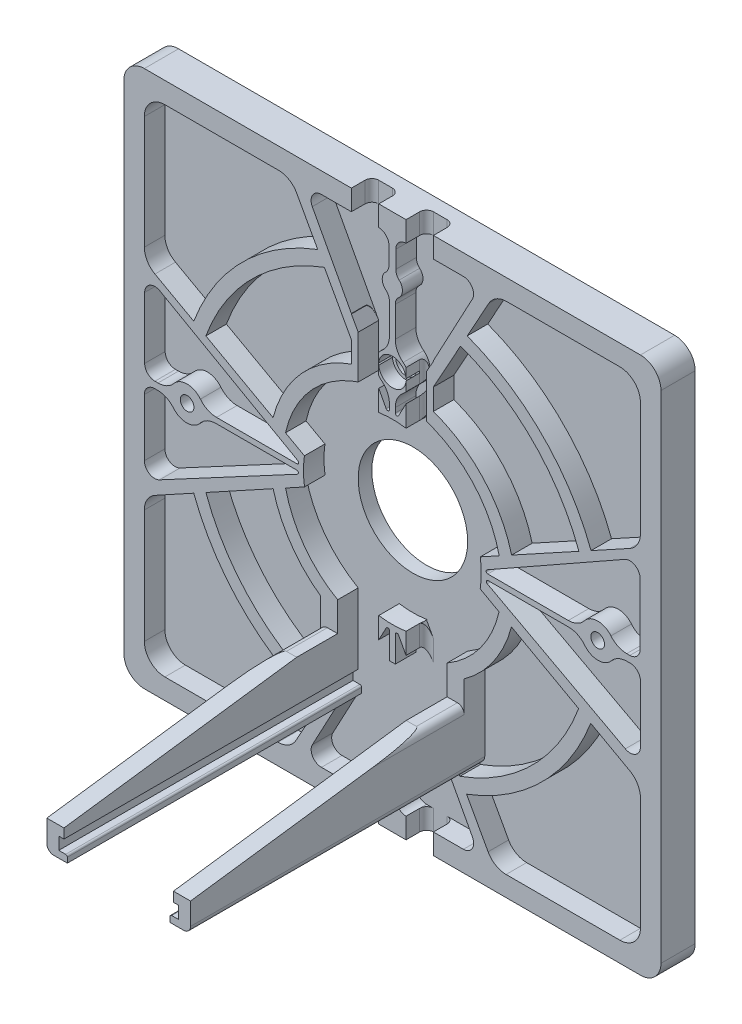
SolidWorks part; units mm, degrees
ref_plane "Спереди" through (0, 0, 0) normal (0, 0, 1) x (1, 0, 0)
ref_plane "Сверху" through (0, 0, 0) normal (0, 1, 0) x (1, 0, 0)
ref_plane "Справа" through (0, 0, 0) normal (1, 0, 0) x (0, 0, -1)
sketch "Эскиз1" plane through (0, 0, 0) normal (0, 0, 1) x (1, 0, 0)
  line L5 (-36.25, -39.25) -> (36.25, -39.25)
  line L6 (-39.25, -36.25) -> (-39.25, 36.25)
  line L7 (-36.25, 39.25) -> (36.25, 39.25)
  line L8 (39.25, -36.25) -> (39.25, 36.25)
  arc A0 (-36.25, -39.25) -> (-39.25, -36.25) centre (-36.25, -36.25) cw
  arc A1 (36.25, -39.25) -> (39.25, -36.25) centre (36.25, -36.25) ccw
  arc A2 (36.25, 39.25) -> (39.25, 36.25) centre (36.25, 36.25) cw
  arc A3 (-39.25, 36.25) -> (-36.25, 39.25) centre (-36.25, 36.25) cw
  dimension "D1" = 3
extrude "Бобышка-Вытянуть2" add sketch "Эскиз1" along normal blind 5
sketch "Эскиз6" plane through (0, 0, 5) normal (0, 0, 1) x (1, 0, 0)
  circle A0 centre (0, 0) radius 13
extrude "Вырез-Вытянуть2" cut sketch "Эскиз6" against normal blind 3
sketch "Эскиз10" plane through (0, 0, 5) normal (0, 0, 1) x (1, 0, 0)
  line L10 (-36.25, -33.25) -> (-36.25, -16.6195)
  line L11 (-33.25, -36.25) -> (-16.7128, -36.25)
  line L12 (-34.6933, -13.9895) -> (-12.8452, -2)
  line L13 (-14.0876, -34.7019) -> (-2, -12.8452)
  line L14 (-2, -12.8452) -> (-12.8452, -2)
  line L15 (36.2485, 33.2453) -> (36.2485, 16.6148)
  line L16 (33.2485, 36.2453) -> (16.7113, 36.2453)
  line L17 (34.6917, 13.9847) -> (12.8437, 1.9953)
  line L18 (14.086, 34.6972) -> (1.9985, 12.8405)
  line L19 (1.9985, 12.8405) -> (12.8437, 1.9953)
  line L20 (33.2453, -36.3173) -> (16.6148, -36.3173)
  line L21 (36.2453, -33.3173) -> (36.2453, -16.7802)
  line L22 (13.9847, -34.7606) -> (1.9953, -12.9126)
  line L23 (34.6972, -14.1549) -> (12.8405, -2.0673)
  line L24 (12.8405, -2.0673) -> (1.9953, -12.9126)
  line L25 (-33.25, 36.1811) -> (-16.6195, 36.1811)
  line L26 (-36.25, 33.1811) -> (-36.25, 16.644)
  line L27 (-13.9895, 34.6244) -> (-2, 12.7764)
  line L28 (-34.7019, 14.0187) -> (-12.8452, 1.9311)
  line L29 (-12.8452, 1.9311) -> (-2, 12.7764)
  circle A0 centre (0, 0) radius 13 construction
  arc A1 (-36.25, -16.6195) -> (-34.6933, -13.9895) centre (-33.25, -16.6195) cw
  arc A2 (-16.7128, -36.25) -> (-14.0876, -34.7019) centre (-16.7128, -33.25) ccw
  arc A3 (-36.25, -33.25) -> (-33.25, -36.25) centre (-33.25, -33.25) ccw
  arc A4 (36.2485, 16.6148) -> (34.6917, 13.9847) centre (33.2485, 16.6148) cw
  arc A5 (16.7113, 36.2453) -> (14.086, 34.6972) centre (16.7113, 33.2453) ccw
  arc A6 (36.2485, 33.2453) -> (33.2485, 36.2453) centre (33.2485, 33.2453) ccw
  arc A7 (16.6148, -36.3173) -> (13.9847, -34.7606) centre (16.6148, -33.3173) cw
  arc A8 (36.2453, -16.7802) -> (34.6972, -14.1549) centre (33.2453, -16.7802) ccw
  arc A9 (33.2453, -36.3173) -> (36.2453, -33.3173) centre (33.2453, -33.3173) ccw
  arc A10 (-16.6195, 36.1811) -> (-13.9895, 34.6244) centre (-16.6195, 33.1811) cw
  arc A11 (-36.25, 16.644) -> (-34.7019, 14.0187) centre (-33.25, 16.644) ccw
  arc A12 (-33.25, 36.1811) -> (-36.25, 33.1811) centre (-33.25, 33.1811) ccw
  point P34 (-36.25, -36.25)
  dimension "D1" = 3
extrude "Вырез-Вытянуть4" cut sketch "Эскиз10" against normal blind 3
sketch "Эскиз12" plane through (0, 0, 2) normal (0, 0, 1) x (1, 0, 0)
  circle A0 centre (0, 0) radius 18
  circle A1 centre (0, 0) radius 16
extrude "Бобышка-Вытянуть7" add sketch "Эскиз12" along normal blind 3
sketch "Эскиз18" plane through (0, 0, 2) normal (0, 0, 1) x (1, 0, 0)
  circle A0 centre (0, 0) radius 29
  circle A1 centre (0, 0) radius 31
extrude "Бобышка-Вытянуть10" add sketch "Эскиз18" along normal blind 3
sketch "Эскиз19" plane through (0, 0, 2) normal (0, 0, 1) x (1, 0, 0)
  circle A0 centre (-30, 0) radius 1
  circle A1 centre (30, 0) radius 1
extrude "Вырез-Вытянуть7" cut sketch "Эскиз19" against normal blind 2 and the other way blind 3
chamfer "Фаска6" distance 2 angle 45 2 edges at (-29, 0, 0) (31, 0, 0)
sketch "Эскиз21" plane through (0, 0, 5) normal (0, 0, 1) x (1, 0, 0)
  line L0 (-34.7046, 0.4543) -> (-34.2543, 0.4543)
  line L14 (-25.7046, 0.3762) -> (-13.9439, 0.3789)
  line L17 (-25.761, -0.4346) -> (-13.9898, -0.4346)
  line L18 (-33.9662, 12.24) -> (-13.8209, 0.8465)
  line L19 (-36.2046, 1.9543) -> (-36.2046, 10.9344)
  line L22 (-0.495, -34.7501) -> (-0.495, -32.2046)
  line L23 (-36.25, -2.0051) -> (-36.25, -10.3806)
  line L24 (-34.0421, -11.703) -> (-13.8718, -0.905)
  line L25 (-34.75, -0.5051) -> (-34.2952, -0.5051)
  line L26 (-0.4246, -27.7337) -> (-0.4246, -13.9898)
  line L27 (0.4345, -27.7337) -> (0.4345, -13.9898)
  line L28 (-11.693, -34.0421) -> (-0.895, -13.8718)
  line L29 (-1.995, -36.2501) -> (-10.3705, -36.2501)
  line L30 (2.005, -36.2501) -> (10.3805, -36.2501)
  line L31 (11.7029, -34.0421) -> (0.9049, -13.8718)
  line L32 (0.505, -34.7501) -> (0.505, -32.2046)
  line L38 (0.4928, 34.7538) -> (0.4928, 32.2084)
  line L44 (11.6908, 34.0458) -> (0.8928, 13.8756)
  line L45 (1.9928, 36.2538) -> (10.3683, 36.2538)
  line L46 (-2.0072, 36.2538) -> (-10.3827, 36.2538)
  line L47 (-11.7051, 34.0459) -> (-0.9071, 13.8756)
  line L48 (-0.5072, 34.7538) -> (-0.5072, 32.2084)
  line L50 (-0.4367, 13.9936) -> (-0.4367, 14.7298)
  line L51 (0.4224, 13.9936) -> (0.4224, 14.6764)
  line L52 (0.4224, 27.7375) -> (0.4224, 23.3236)
  line L53 (-0.4367, 27.7375) -> (-0.4367, 23.2702)
  line L54 (34.75, -0.5051) -> (34.2952, -0.5051)
  line L55 (36.25, -2.0051) -> (36.25, -10.3806)
  line L56 (34.0421, -11.703) -> (13.8718, -0.905)
  line L57 (25.761, -0.4346) -> (13.9898, -0.4346)
  line L58 (34.7046, 0.4543) -> (34.2543, 0.4543)
  line L59 (36.2046, 1.9543) -> (36.2046, 10.9344)
  line L60 (33.9662, 12.24) -> (13.8209, 0.8465)
  line L61 (25.7046, 0.3762) -> (13.9439, 0.3789)
  arc A8 (-12.855, 1.9365) -> (-12.8452, -2) centre (0, 0) ccw construction
  arc A9 (-12.855, 1.9365) -> (-12.8452, -2) centre (0, 0) ccw construction
  arc A15 (-36.25, -10.3806) -> (-34.0421, -11.703) centre (-34.75, -10.3806) ccw
  arc A16 (-36.25, -2.0051) -> (-34.75, -0.5051) centre (-34.75, -2.0051) cw
  arc A17 (-36.2046, 10.9344) -> (-33.9662, 12.24) centre (-34.7046, 10.9344) cw
  arc A18 (-36.2046, 1.9543) -> (-34.7046, 0.4543) centre (-34.7046, 1.9543) ccw
  arc A19 (-13.9898, -0.4346) -> (-13.8718, -0.905) centre (-13.9898, -0.6846) cw
  arc A20 (-13.9439, 0.3789) -> (-13.8209, 0.8465) centre (-13.944, 0.6289) ccw
  arc A22 (0.9636, -28.8771) -> (0.9985, -31.0924) centre (0.01, -30.0001) cw
  arc A23 (-0.9537, -28.8771) -> (-0.9886, -31.0924) centre (-0.0001, -30.0001) ccw
  arc A24 (-0.9886, -31.0924) -> (-0.495, -32.2046) centre (-1.995, -32.2046) cw
  arc A25 (-0.4246, -27.7337) -> (-0.9537, -28.8771) centre (-1.9246, -27.7337) cw
  arc A26 (0.4345, -27.7337) -> (0.9636, -28.8771) centre (1.9345, -27.7337) ccw
  arc A27 (0.9985, -31.0924) -> (0.505, -32.2046) centre (2.005, -32.2046) ccw
  arc A28 (10.3805, -36.2501) -> (11.7029, -34.0421) centre (10.3805, -34.7501) ccw
  arc A29 (2.005, -36.2501) -> (0.505, -34.7501) centre (2.005, -34.7501) cw
  arc A30 (-10.3705, -36.2501) -> (-11.693, -34.0421) centre (-10.3705, -34.7501) cw
  arc A31 (-1.995, -36.2501) -> (-0.495, -34.7501) centre (-1.995, -34.7501) ccw
  arc A32 (0.4345, -13.9898) -> (0.9049, -13.8718) centre (0.6845, -13.9898) cw
  arc A33 (-0.4246, -13.9898) -> (-0.895, -13.8718) centre (-0.6746, -13.9898) ccw
  arc A46 (-0.9658, 28.8809) -> (-1.0007, 31.0961) centre (-0.0122, 30.0038) cw
  arc A47 (0.9515, 28.8809) -> (0.9864, 31.0961) centre (-0.0021, 30.0038) ccw
  arc A48 (0.9864, 31.0961) -> (0.4928, 32.2084) centre (1.9928, 32.2084) cw
  arc A49 (0.4224, 27.7375) -> (0.9515, 28.8809) centre (1.9224, 27.7375) cw
  arc A50 (-0.4367, 27.7375) -> (-0.9658, 28.8809) centre (-1.9367, 27.7375) ccw
  arc A51 (-1.0007, 31.0961) -> (-0.5072, 32.2084) centre (-2.0072, 32.2084) ccw
  arc A52 (-10.3827, 36.2538) -> (-11.7051, 34.0459) centre (-10.3827, 34.7538) ccw
  arc A53 (-2.0072, 36.2538) -> (-0.5072, 34.7538) centre (-2.0072, 34.7538) cw
  arc A54 (10.3683, 36.2538) -> (11.6908, 34.0458) centre (10.3683, 34.7538) cw
  arc A55 (1.9928, 36.2538) -> (0.4928, 34.7538) centre (1.9928, 34.7538) ccw
  arc A56 (-0.4367, 13.9936) -> (-0.9071, 13.8756) centre (-0.6867, 13.9936) cw
  arc A57 (0.4224, 13.9936) -> (0.8928, 13.8756) centre (0.6724, 13.9936) ccw
  arc A60 (-1.542, 17.0558) -> (-1.542, 20.9442) centre (0.0417, 19) cw
  arc A61 (1.5709, 17.0369) -> (1.5709, 20.9631) centre (0.0311, 19) ccw
  arc A62 (0.4224, 14.6764) -> (1.5709, 17.0369) centre (3.4224, 14.6764) cw
  arc A63 (-0.4367, 14.7298) -> (-1.542, 17.0558) centre (-3.4367, 14.7298) ccw
  arc A64 (0.4224, 23.3236) -> (1.5709, 20.9631) centre (3.4224, 23.3236) ccw
  arc A65 (-0.4367, 23.2702) -> (-1.542, 20.9442) centre (-3.4367, 23.2702) cw
  arc A67 (-31.94, 1.5454) -> (-28.0541, 1.5099) centre (-30.0114, -0.0454) cw
  arc A68 (-31.9834, -1.5932) -> (-28.1042, -1.5612) centre (-30.0568, 0) ccw
  arc A69 (-25.7046, 0.3762) -> (-28.0541, 1.5099) centre (-25.7053, 3.3762) cw
  arc A70 (-25.761, -0.4346) -> (-28.1042, -1.5612) centre (-25.761, -3.4346) ccw
  arc A71 (-34.2952, -0.5051) -> (-31.9834, -1.5932) centre (-34.2952, -3.5051) cw
  arc A72 (-34.2543, 0.4543) -> (-31.94, 1.5454) centre (-34.2543, 3.4543) ccw
  arc A73 (36.25, -2.0051) -> (34.75, -0.5051) centre (34.75, -2.0051) ccw
  arc A74 (36.25, -10.3806) -> (34.0421, -11.703) centre (34.75, -10.3806) cw
  arc A75 (13.9898, -0.4346) -> (13.8718, -0.905) centre (13.9898, -0.6846) ccw
  arc A76 (25.761, -0.4346) -> (28.1042, -1.5612) centre (25.761, -3.4346) cw
  arc A77 (34.2952, -0.5051) -> (31.9834, -1.5932) centre (34.2952, -3.5051) ccw
  arc A78 (31.9834, -1.5932) -> (28.1042, -1.5612) centre (30.0568, 0) cw
  arc A79 (36.2046, 1.9543) -> (34.7046, 0.4543) centre (34.7046, 1.9543) cw
  arc A80 (36.2046, 10.9344) -> (33.9662, 12.24) centre (34.7046, 10.9344) ccw
  arc A81 (13.9439, 0.3789) -> (13.8209, 0.8465) centre (13.944, 0.6289) cw
  arc A82 (25.7046, 0.3762) -> (28.0541, 1.5099) centre (25.7053, 3.3762) ccw
  arc A83 (34.2543, 0.4543) -> (31.94, 1.5454) centre (34.2543, 3.4543) cw
  arc A84 (31.94, 1.5454) -> (28.0541, 1.5099) centre (30.0114, -0.0454) ccw
  point P39 (-12.9945, 0.3791)
  point P148 (0.4224, 16.5359)
  point P151 (-0.4367, 16.5384)
  dimension "D1" = 3
  dimension "D2" = 0.25
  dimension "D3" = 3
extrude "Вырез-Вытянуть8" cut sketch "Эскиз21" against normal blind 3
sketch "Эскиз22" plane through (0, 48.4151, 2) normal (0, 0, 1) x (1, 0, 0)
  line L52 (-8.75, -74.3614) -> (-7.75, -74.3614)
  line L53 (-8.75, -72.5614) -> (-8.75, -74.3614)
  line L58 (-10.5, -67.5575) -> (-10.5, -71.5614)
  line L59 (-10.5, -71.5614) -> (-10.5, -72.0614)
  line L60 (-10.5, -74.3614) -> (-10.5, -72.0614)
  line L64 (-8.75, -72.5614) -> (-8, -72.5614)
  line L65 (-9.5, -75.3614) -> (-7.5, -75.3614)
  line L66 (-7.5, -75.3614) -> (-7.5, -74.6114)
  line L67 (-9.5, -66.5575) -> (-8, -66.5575)
  line L68 (-8, -66.5575) -> (-8, -72.5614)
  line L70 (9.5, -66.5575) -> (8, -66.5575)
  line L71 (10.5, -67.5575) -> (10.5, -71.5614)
  line L72 (10.5, -71.5614) -> (10.5, -72.0614)
  line L73 (10.5, -74.3614) -> (10.5, -72.0614)
  line L74 (9.5, -75.3614) -> (7.5, -75.3614)
  line L75 (7.5, -75.3614) -> (7.5, -74.6114)
  line L76 (8.75, -74.3614) -> (7.75, -74.3614)
  line L77 (8.75, -72.5614) -> (8.75, -74.3614)
  line L78 (8.75, -72.5614) -> (8, -72.5614)
  line L79 (8, -66.5575) -> (8, -72.5614)
  arc A18 (9.5, -66.5575) -> (10.5, -67.5575) centre (9.5, -67.5575) cw
  arc A26 (-7.75, -74.3614) -> (-7.5, -74.6114) centre (-7.75, -74.6114) cw
  arc A29 (-9.5, -66.5575) -> (-10.5, -67.5575) centre (-9.5, -67.5575) ccw
  arc A30 (-9.5, -75.3614) -> (-10.5, -74.3614) centre (-9.5, -74.3614) cw
  arc A31 (9.5, -75.3614) -> (10.5, -74.3614) centre (9.5, -74.3614) ccw
  arc A32 (7.75, -74.3614) -> (7.5, -74.6114) centre (7.75, -74.6114) ccw
  point P0 (0, 0)
sketch "Эскиз27" plane through (0, -39.25, 0) normal (0, -1, 0) x (-1, 0, 0)
  line L15 (36.25, -5) -> (-36.25, -5) construction
  line L17 (1.995, -5) -> (5.9932, -5)
  line L22 (5.9932, -5) -> (5.9932, -3)
  line L23 (4.9932, -2) -> (2.995, -2)
  line L24 (1.995, -3) -> (1.995, -5)
  line L29 (-1.995, -3) -> (-1.995, -5)
  line L30 (-4.9932, -2) -> (-2.995, -2)
  line L31 (-5.9932, -5) -> (-5.9932, -3)
  line L32 (-1.995, -5) -> (-5.9932, -5)
  arc A0 (2.995, -2) -> (1.995, -3) centre (2.995, -3) ccw
  arc A1 (5.9932, -3) -> (4.9932, -2) centre (4.9932, -3) ccw
  arc A4 (-2.995, -2) -> (-1.995, -3) centre (-2.995, -3) cw
  arc A5 (-5.9932, -3) -> (-4.9932, -2) centre (-4.9932, -3) cw
  dimension "D1" = 1
extrude "Вырез-Вытянуть12" cut sketch "Эскиз27" against normal blind 78.5
sketch "Эскиз28" plane through (0, 0, 2) normal (0, 0, 1) x (1, 0, 0)
  line L0 (-5.9932, -14.8352) -> (-5.9932, -23.3951)
  line L1 (-5.9932, -23.3951) -> (-4.9932, -21.5271)
  line L2 (-4.9932, -21.5271) -> (-4.9932, -15.2009)
  line L3 (-4.9932, -15.2009) -> (-5.9932, -14.8352)
  line L4 (5.9932, -14.8352) -> (5.9932, -23.3765)
  line L5 (5.9932, -23.3765) -> (4.9932, -21.5085)
  line L6 (4.9932, -21.5085) -> (4.9932, -15.2009)
  line L7 (4.9932, -15.2009) -> (5.9932, -14.8352)
  line L8 (-4.9932, 15.2009) -> (-4.9932, 21.5081)
  line L9 (-4.9932, 21.5081) -> (-5.9932, 23.3125)
  line L10 (-5.9932, 23.3761) -> (-5.9932, 20.053) construction
  line L11 (-5.9932, 23.3125) -> (-5.9932, 14.8352)
  line L12 (-5.9932, 14.8352) -> (-4.9932, 15.2009)
  line L13 (5.9932, 14.8352) -> (5.9932, 23.3125)
  line L14 (5.9932, 23.4029) -> (5.9932, 20.0637) construction
  line L15 (5.9932, 23.3125) -> (4.9932, 21.535)
  line L16 (4.9932, 21.535) -> (4.9932, 15.2009)
  line L17 (4.9932, 15.2009) -> (5.9932, 14.8352)
  arc A0 (-4.9932, 15.2009) -> (-15.6201, 3.4658) centre (0, 0) ccw construction
  arc A1 (-4.9932, 15.2009) -> (-5.9932, 14.8352) centre (0, 0) ccw construction
extrude "Бобышка-Вытянуть12" add sketch "Эскиз28" along normal blind 3
extrude "Бобышка-Вытянуть15" add sketch "Эскиз22" along normal blind 43
sketch "Эскиз36" plane through (-10.5, 0, 0) normal (-1, 0, 0) x (0, 0, 1)
  line L0 (48, -17.3606) -> (5.1996, -17.3606)
  line L2 (48, -19.1424) -> (48, -25.9463) construction
  line L3 (48, -23.1435) -> (48, -17.3606)
  line L4 (5.1996, -17.3606) -> (48, -23.1435)
extrude "Вырез-Вытянуть13" cut sketch "Эскиз36" against normal blind 22
sketch "Эскиз38" plane through (0, 0, 5) normal (0, 0, 1) x (1, 0, 0)
  circle A0 centre (0, 18.9767) radius 2
extrude "Вырез-Вытянуть14" cut sketch "Эскиз38" against normal blind 2
sketch "Эскиз39" plane through (0, 0, 3) normal (0, 0, 1) x (1, 0, 0)
  circle A0 centre (0, 18.9767) radius 1.5
extrude "Вырез-Вытянуть15" cut sketch "Эскиз39" against normal blind 3
sketch "Эскиз43" plane through (0, 0, 5) normal (0, 0, 1) x (1, 0, 0)
  line L2 (-7.5, -26.1963) -> (-7.5, -26.9463)
  line L3 (-7.5, -26.9463) -> (7.5, -26.9463)
  line L4 (7.5, -26.9463) -> (7.5, -26.1963)
  line L8 (8, -24.1463) -> (8, -13.0041)
  line L9 (8, -13.0041) -> (4.2218, -15.0228)
  line L10 (4.2218, -15.0228) -> (2.995, -17.7761)
  line L11 (2.995, -17.7761) -> (-2.995, -17.7947)
  line L12 (-2.995, -17.7947) -> (-4.6348, -13.8953)
  line L13 (-4.6348, -13.8953) -> (-8, -12.9987)
  line L14 (-8, -12.9987) -> (-8, -24.1463)
  line L16 (-8, -24.1463) -> (-8.75, -24.1463)
  line L17 (-8.75, -24.1463) -> (-8.75, -25.9463)
  line L18 (-8.75, -25.9463) -> (-7.75, -25.9463)
  line L19 (8, -24.1463) -> (8.75, -24.1463)
  line L20 (8.75, -24.1463) -> (8.75, -25.9463)
  line L21 (8.75, -25.9463) -> (7.75, -25.9463)
  arc A0 (7.5, -26.1963) -> (7.75, -25.9463) centre (7.75, -26.1963) cw
  arc A1 (-7.75, -25.9463) -> (-7.5, -26.1963) centre (-7.75, -26.1963) cw
  dimension "D1" = 0.25
extrude "Вырез-Вытянуть17" cut sketch "Эскиз43" against normal blind 3
sketch "Эскиз45" plane through (0, 0, 2) normal (0, 0, 1) x (1, 0, 0)
  line L0 (-10.5, -19.1424) -> (-8, -19.1424)
  line L1 (-8, -18.1424) -> (-8, -23.1435) construction
  line L2 (-8, -19.1424) -> (-8, -16.1245)
  line L3 (-8, -16.1245) -> (-10.5, -13.7257)
  line L4 (-10.5, -13.7257) -> (-10.5, -19.1424)
  line L5 (10.5, -19.1424) -> (8, -19.1424)
  line L6 (8, -23.1435) -> (8, -18.1424) construction
  line L7 (8, -19.1424) -> (8, -16.1245)
  line L8 (8, -16.1245) -> (10.5, -13.7257)
  line L9 (10.5, -13.7257) -> (10.5, -19.1424)
extrude "Бобышка-Вытянуть14" add sketch "Эскиз45" along normal blind 3
sketch "Эскиз48" plane through (0, 0, 2) normal (0, 0, 1) x (1, 0, 0)
  circle A2 centre (0, 0) radius 8
extrude "Вырез-Вытянуть23" cut sketch "Эскиз48" against normal blind 3
